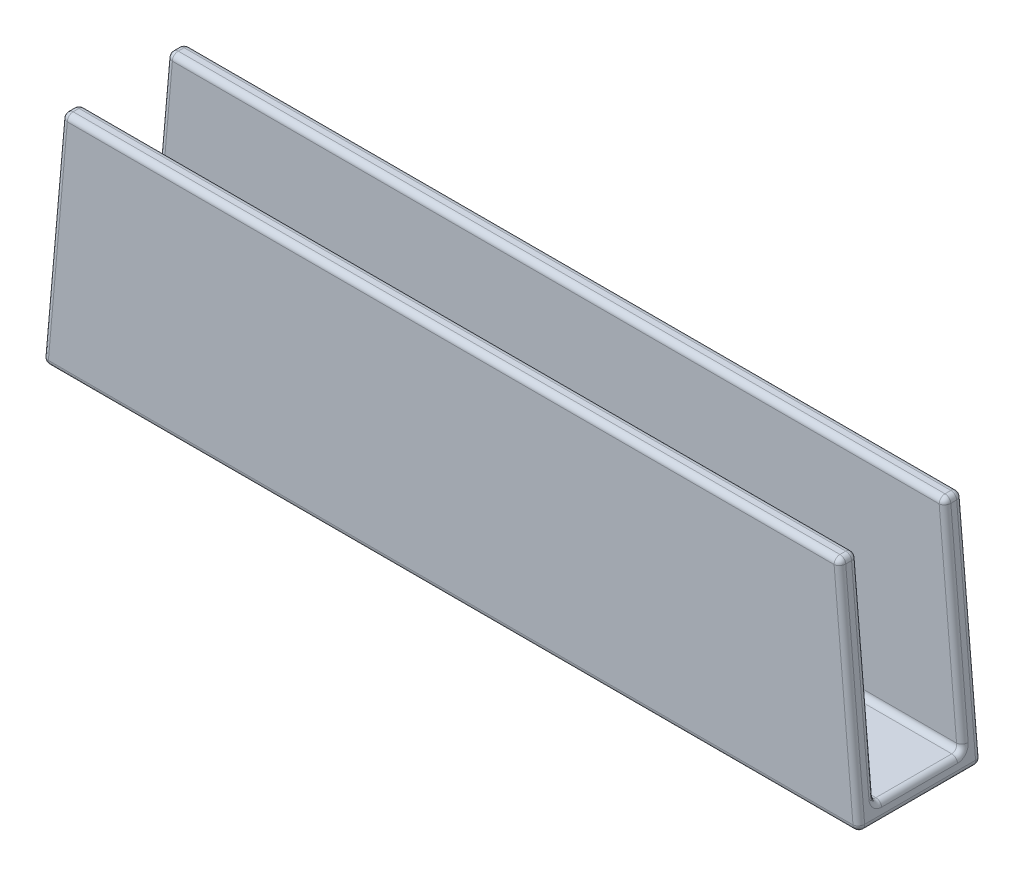
SolidWorks part; units mm, degrees
ref_plane "Front" through (0, 0, 0) normal (0, 0, 1) x (1, 0, 0)
ref_plane "Top" through (0, 0, 0) normal (0, 1, 0) x (1, 0, 0)
ref_plane "Right" through (0, 0, 0) normal (1, 0, 0) x (0, 0, -1)
sketch "Çizim1" plane through (0, 0, 0) normal (0, 0, 1) x (1, 0, 0)
  line L1 (-35, 9.75) -> (35, 9.75)
  line L2 (-35, 9.75) -> (-35, -9.75)
  line L3 (-35, -9.75) -> (35, -9.75)
  line L4 (35, 9.75) -> (35, -9.75)
  line L5 (-35, 9.75) -> (35, -9.75) construction
  line L6 (-35, -9.75) -> (35, 9.75) construction
  point P0 (0, 0)
  dimension "D1" = 19.5
  dimension "D2" = 70
extrude "Yükseklik-Ekstrüzyon1" add sketch "Çizim1" along normal blind 10.5
shell "İç Boşaltma1" thickness 1.5 removed face at (35, 0, 5.25) removed face at (-35, 0, 5.25) removed face at (0, 9.75, 5.25)
fillet "Radyus1" radius 0.5 2 edges at (0, -8.25, 1.5) (0, -8.25, 9)
fillet "Radyus2" radius 0.5 2 edges at (0, -9.75, 0) (0, -9.75, 10.5)
sketch "Çizim2" plane through (0, 0, 0) normal (0, 0, -1) x (-1, 0, 0)
  line L0 (35, -9.75) -> (33.294, 9.75)
  line L1 (-35, 9.75) -> (35, 9.75) construction
  line L2 (33.294, 9.75) -> (35, 9.75)
  line L3 (35, 9.75) -> (35, -9.75)
  dimension "D1" = 5
extrude "Kes-Ekstrüzyon1" cut sketch "Çizim2" against normal blind 23
mirror "Aynalama1" about plane through (0, 0, 0) normal (1, 0, 0) of "Kes-Ekstrüzyon1"
fillet "Radyus3" radius 0.5 28 edges at (34.1251, 0.25, 10.5) (34.9872, -9.6036, 10.3536) (35, -9.75, 5.25) (34.9872, -9.6036, 0.1464) (-34.1251, 0.25, 10.5) (-34.9872, -9.6036, 10.3536) (-35, -9.75, 5.25) (-34.9872, -9.6036, 0.1464) (-34.0595, 1, 1.5) (-34.856, -8.1036, 1.6464) (-34.8688, -8.25, 5.25) (-34.856, -8.1036, 8.8536) (34.0595, 1, 9) (34.856, -8.1036, 8.8536) (34.8688, -8.25, 5.25) (34.856, -8.1036, 1.6464) (0, 9.75, 1.5) (0, 9.75, 0) (0, 9.75, 10.5) (0, 9.75, 9) (33.294, 9.75, 9.75) (33.294, 9.75, 0.75) (34.1251, 0.25, 0) (-34.1251, 0.25, 0) (-33.294, 9.75, 0.75) (-33.294, 9.75, 9.75) (-34.0595, 1, 9) (34.0595, 1, 1.5)
